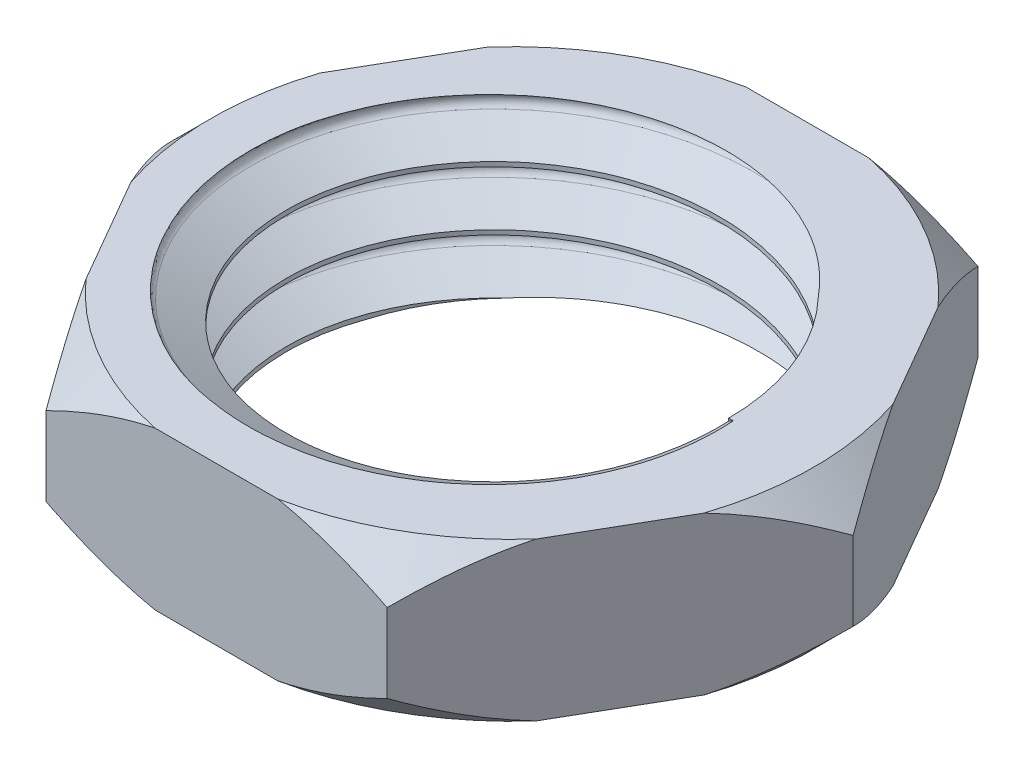
SolidWorks part; units mm, degrees
ref_plane "Front Plane" through (0, 0, 0) normal (0, 0, 1) x (1, 0, 0)
ref_plane "Top Plane" through (0, 0, 0) normal (0, 1, 0) x (1, 0, 0)
ref_plane "Right Plane" through (0, 0, 0) normal (1, 0, 0) x (0, 0, -1)
sketch "Sketch5" plane through (0, 0, 0) normal (0, 1, 0) x (1, 0, 0)
  line L1 (8.6603, 0) -> (4.3301, 7.5)
  line L2 (4.3301, 7.5) -> (-4.3301, 7.5)
  line L3 (-4.3301, 7.5) -> (-8.6603, 0)
  line L4 (-8.6603, 0) -> (-4.3301, -7.5)
  line L5 (-4.3301, -7.5) -> (4.3301, -7.5)
  line L6 (4.3301, -7.5) -> (8.6603, 0)
  circle A0 centre (0, 0) radius 7.5 construction
  circle A1 centre (0, 0) radius 5.5
  dimension "D1" = 15
  dimension "D2" = 11
extrude "Boss-Extrude6" add sketch "Sketch5" along normal blind 4
ref_plane "Plane1" through (0, -1, 0) normal (0, 1, 0) x (1, 0, 0)
sketch "Sketch7" plane through (0, -1, 0) normal (0, -1, 0) x (1, 0, 0)
  circle A2 centre (0, 0) radius 5.5 construction
  circle A3 centre (0, 0) radius 5.5
curve "Helix/Spiral2" pitch 1.5 height 5.625 radius 5.5 centre (0, -1, 0) axis (0, 1, 0) start towards (0, 0, -1)
sketch "Sketch8" plane through (0, 0, 0) normal (1, 0, 0) x (0, 0, -1)
  line L0 (5.5, -1) -> (6.3, -1) construction
  line L1 (6.4, -0.8268) -> (5.5, -0.3072)
  line L2 (5.5, -0.3072) -> (5.5, -1.6928)
  line L3 (5.5, -1.6928) -> (6.4, -1.1732)
  line L4 (6.3, -1) -> (6.5, -1) construction
  arc A0 (6.4, -0.8268) -> (6.4, -1.1732) centre (6.3, -1) cw
  spline S1 degree 3 poles (5.5, -1) (5.5, -0.969) (5.2136, -0.9062) (3.9903, -0.8125) (2.1596, -0.7187) (0, -0.625) (-2.1596, -0.5312) (-3.9903, -0.4375) (-5.2136, -0.3437) (-5.6432, -0.25) (-5.2136, -0.1562) (-3.9903, -0.0625) (-1.5493, 0.0625) (1.5493, 0.1875) (3.9903, 0.3125) (5.2136, 0.4063) (5.6432, 0.5) (5.2136, 0.5938) (3.9903, 0.6875) (1.5493, 0.8125) (-1.5493, 0.9375) (-3.9903, 1.0625) (-5.2136, 1.1563) (-5.6432, 1.25) (-5.2136, 1.3438) (-3.9903, 1.4375) (-1.5493, 1.5625) (1.5493, 1.6875) (3.9903, 1.8125) (5.2136, 1.9063) (5.6432, 2) (5.2136, 2.0938) (3.9903, 2.1875) (1.5493, 2.3125) (-1.5493, 2.4375) (-3.9903, 2.5625) (-5.2136, 2.6563) (-5.6432, 2.75) (-5.2136, 2.8437) (-3.9903, 2.9375) (-1.5493, 3.0625) (1.5493, 3.1875) (3.9903, 3.3125) (5.2136, 3.4062) (5.6432, 3.5) (5.2136, 3.5937) (3.9903, 3.6875) (1.5493, 3.8125) (-1.5493, 3.9375) (-3.9903, 4.0625) (-5.2136, 4.1562) (-5.6431, 4.25) (-5.2138, 4.3437) (-3.9898, 4.4375) (-2.1616, 4.5312) (-0.7153, 4.594) (0, 4.625) knots 0 0 0 0 0.016667 0.033333 0.05 0.066667 0.083333 0.1 0.116667 0.133333 0.15 0.166667 0.183333 0.216667 0.233333 0.25 0.266667 0.283333 0.3 0.316667 0.35 0.366667 0.383333 0.4 0.416667 0.433333 0.45 0.483333 0.5 0.516667 0.533333 0.55 0.566667 0.583333 0.616667 0.633333 0.65 0.666667 0.683333 0.7 0.716667 0.75 0.766667 0.783333 0.8 0.816667 0.833333 0.85 0.883333 0.9 0.916667 0.933333 0.95 0.966667 0.983333 1 1 1 1 construction
  point P1 (0, 0)
  point P8 (0, 0)
  point P9 (5.95, -1)
  point P10 (5.5, -1)
  point P12 (0, 0)
  dimension "D1" = 0.2
  dimension "D2" = 1
  dimension "D3" = 60
sweep "Cut-Sweep2" cut profiles "Sketch8" path "Helix/Spiral2" align with end faces yes
sketch "Sketch10" plane through (0, 0, 0) normal (0, 0, 1) x (1, 0, 0)
  line L0 (7.6603, 4) -> (8.6603, 3)
  line L1 (8.6603, 4) -> (4.3301, 4) construction
  line L2 (8.6603, 4) -> (8.6603, 0) construction
  line L3 (8.6603, 3) -> (8.6603, 1)
  line L4 (8.6603, 1) -> (7.6603, 0)
  line L5 (8.6603, 0) -> (4.3301, 0) construction
  line L6 (7.6603, 0) -> (10.1045, 0)
  line L7 (10.1045, 0) -> (10.1045, 4)
  line L8 (10.1045, 4) -> (7.6603, 4)
  line L9 (0, 0) -> (0, 5.7513) construction
  point P17 (8.6603, 2)
  point P18 (10.1045, 2)
  dimension "D1" = 45
  dimension "D2" = 2
revolve "Cut-Revolve1" cut sketch "Sketch10" angle 360 about L9
